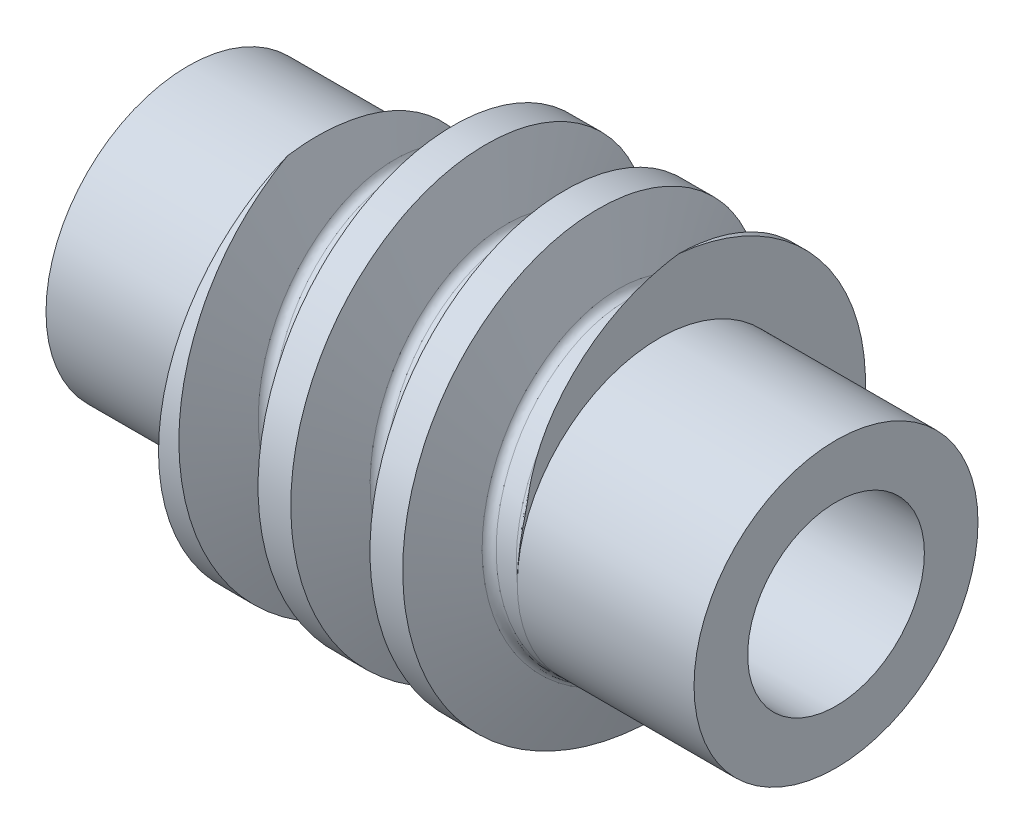
SolidWorks part; units mm, degrees
ref_plane "前视基准面" through (0, 0, 0) normal (0, 0, 1) x (1, 0, 0)
ref_plane "上视基准面" through (0, 0, 0) normal (0, 1, 0) x (1, 0, 0)
ref_plane "右视基准面" through (0, 0, 0) normal (1, 0, 0) x (0, 0, -1)
ref_axis "基准轴1" through (-10.9638, 0, 0) along (1, 0, 0)
sketch "草图1" plane through (0, 0, 0) normal (0, 0, 1) x (1, 0, 0)
  line L0 (-56.8494, 0) -> (118.6822, 0) construction
  line L1 (0, 48.1623) -> (0, -71.9241) construction
  line L2 (0, 3.5) -> (0, 0)
  line L3 (-10.9638, 0) -> (40.5935, 0) construction
  line L7 (0, 3.5) -> (5, 3.5)
  line L13 (0, 0) -> (5, 0)
  line L14 (5, 0) -> (5, 3.5)
  dimension "da1" = 3.5
  dimension "B1" = 5
revolve "旋转1" add sketch "草图1" angle 360 about L0
sketch "草图2" plane through (0, 0, 0) normal (1, 0, 0) x (0, 0, -1)
  circle A0 centre (0, 0) radius 3
  dimension "d1" = 6
sketch "草图3" plane through (0, 0, 0) normal (0, 0, 1) x (1, 0, 0)
  line L0 (0, 25.9401) -> (0, 0) construction
  line L1 (-2.016, 3.5) -> (-0.672, 3.5)
  line L2 (0, 3.5) -> (5, 3.5) construction
  line L3 (-0.672, 3.5) -> (-1.0328, 2.5087)
  line L4 (-1.1737, 2.41) -> (-1.5142, 2.41)
  line L5 (-1.344, 3.5) -> (-1.344, 2.41) construction
  line L6 (0, 0) -> (8.7963, 0) construction
  line L7 (-1.834, 3) -> (-0.854, 3) construction
  line L8 (-1.6552, 2.5087) -> (-2.016, 3.5)
  line L9 (-2.016, 3.5) -> (-2.016, -16.5) construction
  line L10 (-1.344, 3.5) -> (0, 3.5) construction
  arc A0 (-1.6552, 2.5087) -> (-1.5142, 2.41) centre (-1.5142, 2.56) ccw
  arc A1 (-1.1737, 2.41) -> (-1.0328, 2.5087) centre (-1.1737, 2.56) ccw
  point P14 (-1.6192, 2.41)
  point P19 (-1.0687, 2.41)
  dimension "ppn" = 0.15
  dimension "df1" = 4.82
  dimension "d1" = 6
  dimension "0.5px" = 0.98
  dimension "aa1" = 20
  dimension "aa" = 20
sketch "草图4" plane through (0, 0, 0) normal (1, 0, 0) x (0, 0, -1)
  circle A0 centre (0, 0) radius 2.41
sketch "草图5" plane through (5, 0, 0) normal (1, 0, 0) x (0, 0, -1)
  circle A0 centre (0, 0) radius 2.41 construction
  circle A1 centre (0, 0) radius 2.41
curve "螺旋线/涡状线1" pitch 1.9 height 17.1 radius 3 centre (0, 0, 0) axis (1, 0, 0) start towards (0, 1, 0)
sweep "切除-扫描1" cut profiles "草图3" path "螺旋线/涡状线1" align with end faces yes
extrude "凸台-拉伸1" add sketch "草图4" against normal blind 3
extrude "凸台-拉伸2" add sketch "草图5" along normal blind 3
hole_wizard "Ø3.0 (3) 直径孔1" positions "草图7" profile "草图8" hole size "Ø3.0" standard "GB"
sketch "草图7" plane through (8, 0, 0) normal (1, 0, 0) x (0, 0, -1)
  point P0 (0, 0)
sketch "草图8" plane through (8, 0, 0) normal (0, 1, 0) x (0, 0, -1)
  line L0 (0, 0) -> (0, 31.2213)
  line L1 (0, 31.2213) -> (1.5, 30.32)
  line L2 (1.5, 30.32) -> (1.5, 0)
  line L5 (1.5, 0) -> (0, 0)
  line L10 (0, 31.2213) -> (-1.5, 30.32) construction
  line L11 (0, -6.35) -> (0, 107.95) construction
  dimension "孔直径" = 3
  dimension "孔深度" = 30.32
  dimension "导头角度" = 118
sketch "草图9" plane through (0, 0, 0) normal (1, 0, 0) x (0, 0, -1)
  circle A0 centre (0, 0) radius 3 construction
  dimension "D1" = 6
